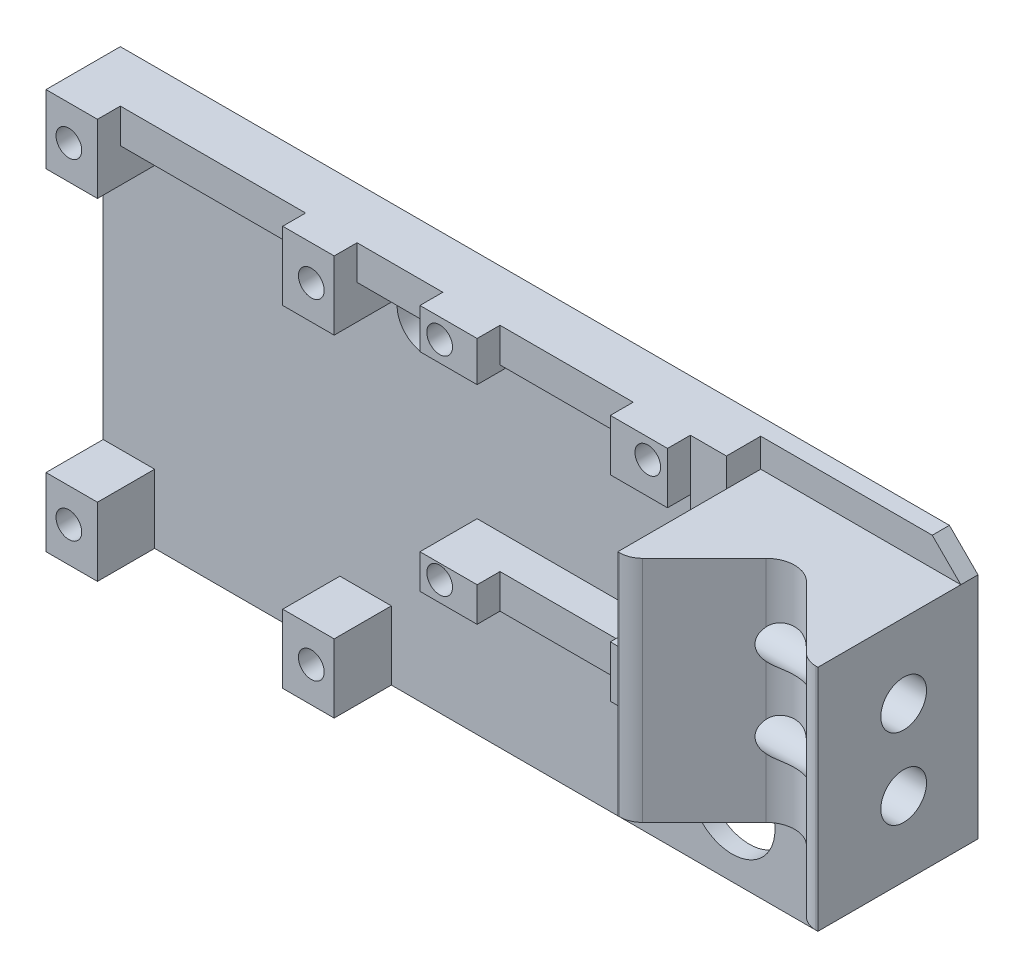
SolidWorks part; units mm, degrees
ref_plane "Plan de face" through (0, 0, 0) normal (0, 0, 1) x (1, 0, 0)
ref_plane "Plan de dessus" through (0, 0, 0) normal (0, 1, 0) x (1, 0, 0)
ref_plane "Plan de droite" through (0, 0, 0) normal (1, 0, 0) x (0, 0, -1)
sketch "Esquisse1" plane through (0, 0, 0) normal (0, 0, 1) x (1, 0, 0)
  line L1 (0, 0) -> (150, 0)
  line L2 (0, 0) -> (0, 70)
  line L3 (0, 70) -> (150, 70)
  line L4 (150, 0) -> (150, 70)
  dimension "D1" = 150
  dimension "D2" = 70
extrude "Boss.-Extru.1" add sketch "Esquisse1" along normal blind 3
sketch "Esquisse2" plane through (0, 0, 3) normal (0, 0, 1) x (1, 0, 0)
  line L1 (0, 0) -> (0, 70) construction
  line L2 (0, 70) -> (50.4, 70) construction
  line L3 (150, 70) -> (0, 70) construction
  line L4 (50.4, 70) -> (50.4, 0) construction
  line L5 (0, 0) -> (150, 0) construction
  line L6 (50.4, 0) -> (0, 0) construction
  line L7 (0, 70) -> (9, 70)
  line L8 (0, 70) -> (0, 58)
  line L9 (0, 58) -> (9, 58)
  line L10 (9, 70) -> (9, 58)
  circle A0 centre (4, 63.9) radius 2.25
  point P14 (25.2, 70)
  point P15 (0, 35)
  dimension "D2" = 4.5
  dimension "D1" = 50.4
  dimension "D3" = 21.2
  dimension "D4" = 28.9
  dimension "D5" = 12
  dimension "D6" = 9
extrude "Boss.-Extru.2" add sketch "Esquisse2" along normal blind 10
ref_plane "Plan1" through (0, 35, 0) normal (0, -1, 0) x (-1, 0, 0)
ref_plane "Plan2" through (25.2, 0, 0) normal (-1, 0, 0) x (0, 0, 1)
mirror "Symétrie1" about plane through (25.2, 0, 0) normal (-1, 0, 0) of "Boss.-Extru.2"
mirror "Symétrie2" about plane through (0, 35, 0) normal (0, -1, 0) of "Symétrie1"
sketch "Esquisse3" plane through (0, 0, 3) normal (0, 0, 1) x (1, 0, 0)
  line L0 (150, 70) -> (50.4, 70) construction
  line L1 (65.4, 70) -> (75.4, 70)
  line L2 (65.4, 70) -> (65.4, 64)
  line L3 (65.4, 64) -> (75.4, 64)
  line L4 (75.4, 70) -> (75.4, 64)
  line L5 (65.4, 70) -> (65.4, 26.7) construction
  line L6 (65.4, 26.7) -> (108.7, 26.7) construction
  line L7 (108.7, 26.7) -> (108.7, 70) construction
  line L8 (108.7, 70) -> (65.4, 70) construction
  line L9 (50.4, 70) -> (50.4, 58) construction
  circle A0 centre (68.85, 66.55) radius 2.25
  point P8 (87.05, 70)
  point P14 (65.4, 48.35)
  dimension "D8" = 4.5
  dimension "D1" = 6
  dimension "D2" = 10
  dimension "D3" = 18.2
  dimension "D4" = 43.3
  dimension "D5" = 43.3
  dimension "D6" = 15
  dimension "D7" = 18.2
extrude "Boss.-Extru.3" add sketch "Esquisse3" along normal blind 10
ref_plane "Plan3" through (87.05, 0, 0) normal (-1, 0, 0) x (0, 0, 1)
ref_plane "Plan4" through (0, 48.35, 0) normal (0, 1, 0) x (1, 0, 0)
mirror "Symétrie3" about plane through (87.05, 0, 0) normal (-1, 0, 0) of "Boss.-Extru.3"
mirror "Symétrie4" about plane through (0, 48.35, 0) normal (0, 1, 0) of "Symétrie3"
sketch "Esquisse4" plane through (0, 35, 0) normal (0, -1, 0) x (-1, 0, 0)
  line L0 (-150, -3) -> (-150, -28)
  line L1 (-150, -28) -> (-148, -28)
  line L2 (-148, -28) -> (-132.5, -12.5)
  line L3 (-132.5, -12.5) -> (-117, -28)
  line L4 (-117, -28) -> (-115, -28)
  line L5 (-115, -28) -> (-115, -3)
  line L6 (-50.4, -3) -> (-150, -3) construction
  line L7 (-115, -3) -> (-150, -3)
  dimension "D1" = 45
  dimension "D2" = 45
  dimension "D3" = 25
  dimension "D4" = 25
  dimension "D5" = 2
  dimension "D6" = 2
  dimension "D7" = 35
extrude "Boss.-Extru.4" add sketch "Esquisse4" along normal blind 10 and the other way blind 30
fillet "Congé1" radius 5 1 edges at (132.5, 45, 12.5)
fillet "Congé2" radius 4 2 edges at (148, 45, 28) (117, 45, 28)
sketch "Esquisse5" plane through (150, 0, 0) normal (1, 0, 0) x (0, 0, -1)
  line L0 (-28, 65) -> (-28, 25) construction
  line L1 (-3, 65) -> (-3, 25) construction
  circle A0 centre (-13, 52) radius 4
  circle A1 centre (-13, 38) radius 4
  point P4 (-28, 45)
  dimension "D3" = 8
  dimension "D6" = 8
  dimension "D1" = 7
  dimension "D2" = 10
  dimension "D4" = 0
  dimension "D5" = 7
extrude "Enlèv. mat.-Extru.1" cut sketch "Esquisse5" against normal up to surface (35 mm away) up to face at (115, 45, 15.5)
sketch "Esquisse6" plane through (0, 0, 3) normal (0, 0, 1) x (1, 0, 0)
  line L1 (75.4, 70) -> (98.7, 70)
  line L2 (75.4, 70) -> (75.4, 64)
  line L3 (75.4, 64) -> (98.7, 64)
  line L4 (98.7, 70) -> (98.7, 64)
  line L5 (98.7, 32.7) -> (75.4, 32.7)
  line L6 (98.7, 32.7) -> (98.7, 26.7)
  line L7 (98.7, 26.7) -> (75.4, 26.7)
  line L8 (75.4, 32.7) -> (75.4, 26.7)
  line L9 (108.7, 70) -> (115, 70)
  line L10 (108.7, 70) -> (108.7, 25)
  line L11 (108.7, 25) -> (115, 25)
  line L12 (115, 70) -> (115, 25)
extrude "Boss.-Extru.5" add sketch "Esquisse6" along normal blind 6
chamfer "Chanfrein1" distance 1.7 angle 45 1 edges at (108.7, 25, 6)
sketch "Esquisse7" plane through (0, 0, 3) normal (0, 0, 1) x (1, 0, 0)
  line L0 (41.4, 58) -> (41.4, 70) construction
  line L1 (50.4, 70) -> (65.4, 70)
  line L2 (50.4, 70) -> (50.4, 64)
  line L3 (50.4, 64) -> (65.4, 64)
  line L4 (65.4, 70) -> (65.4, 64)
  line L5 (9, 70) -> (41.4, 70)
  line L6 (9, 70) -> (9, 64)
  line L7 (9, 64) -> (41.4, 64)
  line L8 (41.4, 70) -> (41.4, 64)
  dimension "D1" = 0
extrude "Boss.-Extru.6" add sketch "Esquisse7" along normal up to surface (6 mm away) up to face at (87.05, 67, 9)
chamfer "Chanfrein2" distance 5 angle 45 1 edges at (150, 70, 1.5)
chamfer "Chanfrein3" distance 25 angle 45 1 edges at (150, 0, 1.5)
sketch "Esquisse8" plane through (0, 0, 3) normal (0, 0, 1) x (1, 0, 0)
  line L0 (50.4, 64) -> (108.7, 64) construction
  line L1 (50.4, 64) -> (50.4, 58) construction
  circle A0 centre (56.4, 58) radius 5
  dimension "D1" = 10
  dimension "D2" = 6
  dimension "D3" = 6
extrude "Enlèv. mat.-Extru.2" cut sketch "Esquisse8" against normal through all
sketch "Esquisse9" plane through (0, 0, 3) normal (0, 0, 1) x (1, 0, 0)
  line L0 (65.4, 26.7) -> (108.7, 26.7) construction
  circle A0 centre (110, 11.7) radius 7.5
  dimension "D1" = 15
  dimension "D2" = 15
  dimension "D3" = 15
extrude "Enlèv. mat.-Extru.3" cut sketch "Esquisse9" against normal through all
sketch "Esquisse10" plane through (0, 0, 3) normal (0, 0, 1) x (1, 0, 0)
  line L0 (108.7, 64) -> (108.7, 32.7) construction
  line L1 (65.4, 64) -> (75.4, 64)
  line L2 (65.4, 64) -> (65.4, 63)
  line L3 (65.4, 63) -> (75.4, 63)
  line L4 (75.4, 64) -> (75.4, 63)
  line L5 (98.7, 64) -> (108.7, 64)
  line L6 (98.7, 64) -> (98.7, 61)
  line L7 (98.7, 61) -> (108.7, 61)
  line L8 (108.7, 64) -> (108.7, 61)
  line L9 (75.4, 70) -> (65.4, 70) construction
  line L10 (98.7, 32.7) -> (108.7, 32.7)
  line L11 (98.7, 32.7) -> (98.7, 35.7)
  line L12 (98.7, 35.7) -> (108.7, 35.7)
  line L13 (108.7, 32.7) -> (108.7, 35.7)
  line L14 (98.7, 70) -> (108.7, 70) construction
  line L15 (98.7, 26.7) -> (108.7, 26.7) construction
  dimension "D1" = 7
  dimension "D2" = 10
  dimension "D3" = 9
  dimension "D4" = 9
extrude "Boss.-Extru.7" add sketch "Esquisse10" along normal up to surface (10 mm away) up to face at (70.4, 67, 13)
